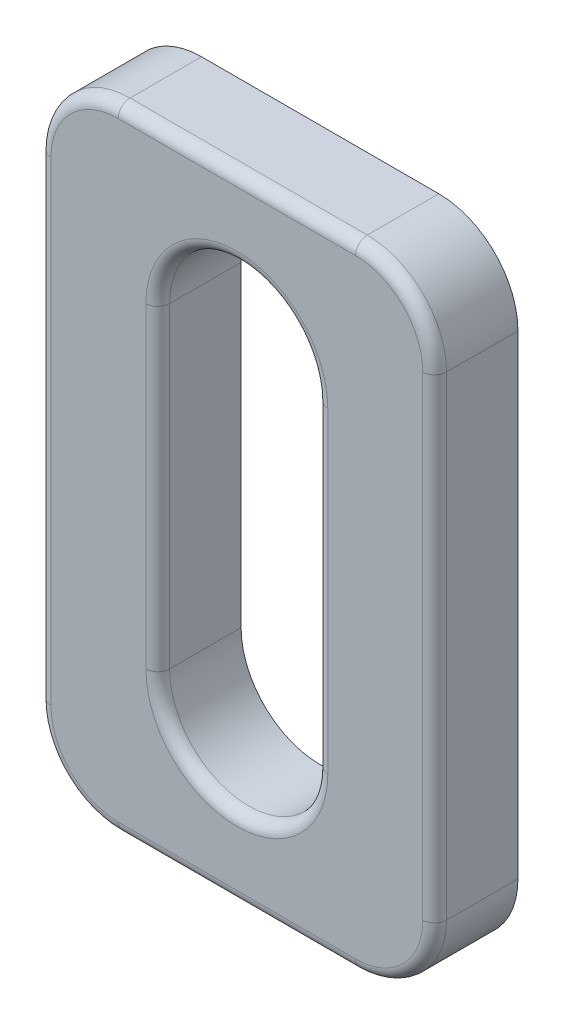
SolidWorks part; units mm, degrees
material "ABS"
ref_plane "Front Plane" through (0, 0, 0) normal (0, 0, 1) x (1, 0, 0)
ref_plane "Top Plane" through (0, 0, 0) normal (0, 1, 0) x (1, 0, 0)
ref_plane "Right Plane" through (0, 0, 0) normal (1, 0, 0) x (0, 0, -1)
sketch "Sketch1" plane through (0, 0, 0) normal (0, 0, 1) x (1, 0, 0)
  line L0 (12.5, 40) -> (12.5, 20) construction
  line L1 (0, 0) -> (25, 0)
  line L2 (0, 0) -> (0, 40)
  line L3 (0, 40) -> (25, 40)
  line L4 (25, 0) -> (25, 40)
  line L5 (12.5, 20) -> (12.5, 0) construction
  line L6 (12.5, 30) -> (12.5, 10) construction
  line L7 (17.5, 30) -> (17.5, 10)
  line L8 (7.5, 30) -> (7.5, 10)
  arc A0 (17.5, 30) -> (7.5, 30) centre (12.5, 30) ccw
  arc A1 (7.5, 10) -> (17.5, 10) centre (12.5, 10) ccw
  point P10 (12.5, 20)
  dimension "D3" = 5
  dimension "D1" = 25
  dimension "D2" = 40
extrude "Boss-Extrude1" add sketch "Sketch1" along normal blind 5.2671
fillet "Fillet1" radius 5 4 edges at (25, 40, 2.6336) (25, 0, 2.6336) (0, 0, 2.6336) (0, 40, 2.6336)
fillet "Fillet2" radius 0.75 12 edges at (1.4645, 1.4645, 5.2671) (0, 20, 5.2671) (1.4645, 38.5355, 5.2671) (23.5355, 38.5355, 5.2671) (12.5, 40, 5.2671) (25, 20, 5.2671) (23.5355, 1.4645, 5.2671) (12.5, 0, 5.2671) (12.5, 5, 5.2671) (17.5, 20, 5.2671) (12.5, 35, 5.2671) (7.5, 20, 5.2671)
